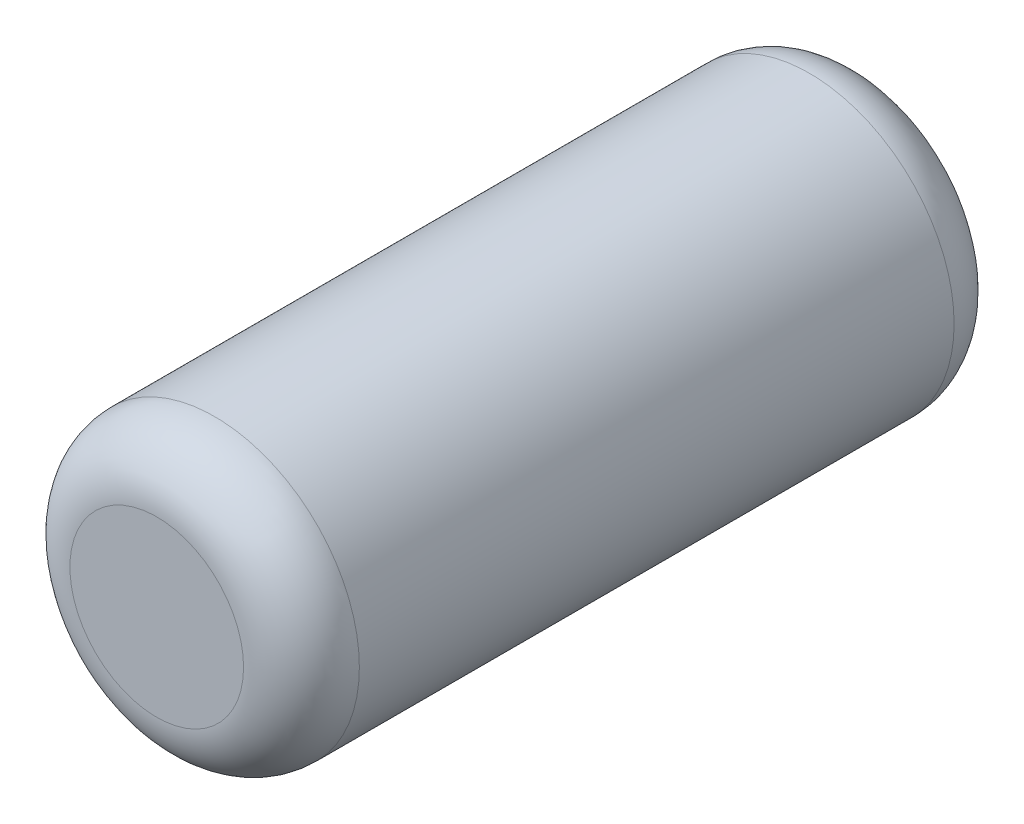
SolidWorks part; units mm, degrees
ref_plane "Front Plane" through (0, 0, 0) normal (0, 0, 1) x (1, 0, 0)
ref_plane "Top Plane" through (0, 0, 0) normal (0, 1, 0) x (1, 0, 0)
ref_plane "Right Plane" through (0, 0, 0) normal (1, 0, 0) x (0, 0, -1)
sketch "Sketch1" plane through (0, 0, 0) normal (0, 0, 1) x (1, 0, 0)
  circle A0 centre (0, 0) radius 34.925
extrude "Boss-Extrude1" add sketch "Sketch1" along normal blind 171.45
fillet "Fillet1" radius 13.97 2 edges at (34.925, 0, 171.45) (34.925, 0, 0)
